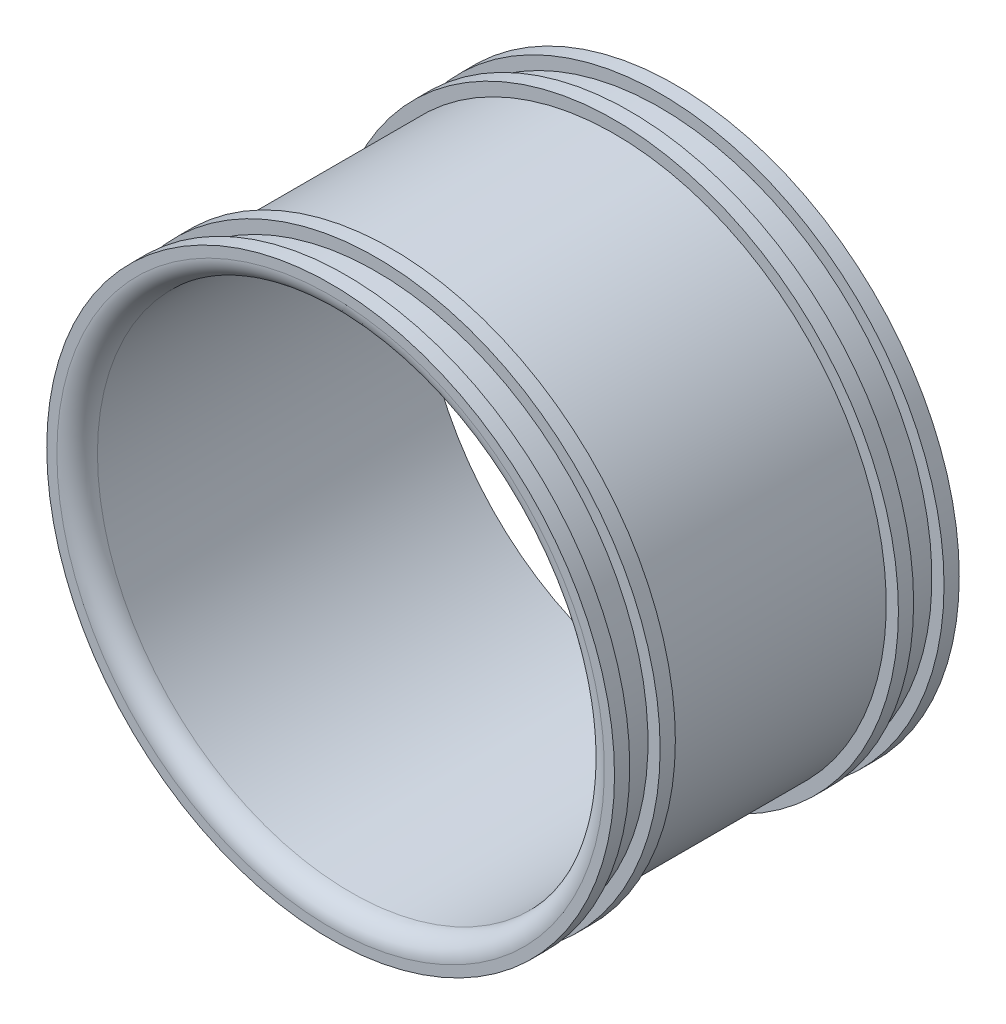
SolidWorks part; units mm, degrees
ref_plane "Front Plane" through (0, 0, 0) normal (0, 0, 1) x (1, 0, 0)
ref_plane "Top Plane" through (0, 0, 0) normal (0, 1, 0) x (1, 0, 0)
ref_plane "Right Plane" through (0, 0, 0) normal (1, 0, 0) x (0, 0, -1)
ref_plane "Plane1" through (0, 0, 0) normal (0, -1, 0) x (1, 0, 0)
sketch "Sketch1" plane through (0, 0, 0) normal (0, -1, 0) x (1, 0, 0)
  line L2 (25, 0) -> (28, 0)
  line L3 (28, 0) -> (28, 1.5)
  line L4 (28, 1.5) -> (26.8, 1.5)
  line L5 (26.8, 1.5) -> (26.8, 4.5)
  line L6 (26.8, 4.5) -> (28, 4.5)
  line L7 (28, 4.5) -> (28, 6)
  line L8 (28, 6) -> (26.8, 6)
  line L9 (26.8, 6) -> (26.8, 28)
  line L10 (26.8, 28) -> (28, 28)
  line L11 (28, 28) -> (28, 29.5)
  line L12 (28, 29.5) -> (26.8, 29.5)
  line L13 (26.8, 29.5) -> (26.8, 32.5)
  line L14 (26.8, 32.5) -> (28, 32.5)
  line L15 (28, 32.5) -> (28, 34)
  line L16 (0, 34) -> (0, 0) construction
  line L17 (25, 0) -> (25, 32)
  line L19 (0, 0) -> (25, 0) construction
  line L20 (27, 34) -> (28, 34)
  arc A0 (25, 32) -> (27, 34) centre (27, 32) cw
  dimension "D5" = 2
  dimension "D1" = 1.5
  dimension "D2" = 1.2
  dimension "D3" = 3
  dimension "D4" = 25
  dimension "D6" = 32
  dimension "D7" = 3
  dimension "D8" = 1.2
  dimension "D9" = 1.5
  dimension "D10" = 22
  dimension "D11" = 3
  dimension "D12" = 1.5
  dimension "D13" = 25
revolve "Revolve1" add sketch "Sketch1" angle 360 about L16 reverse direction yes
